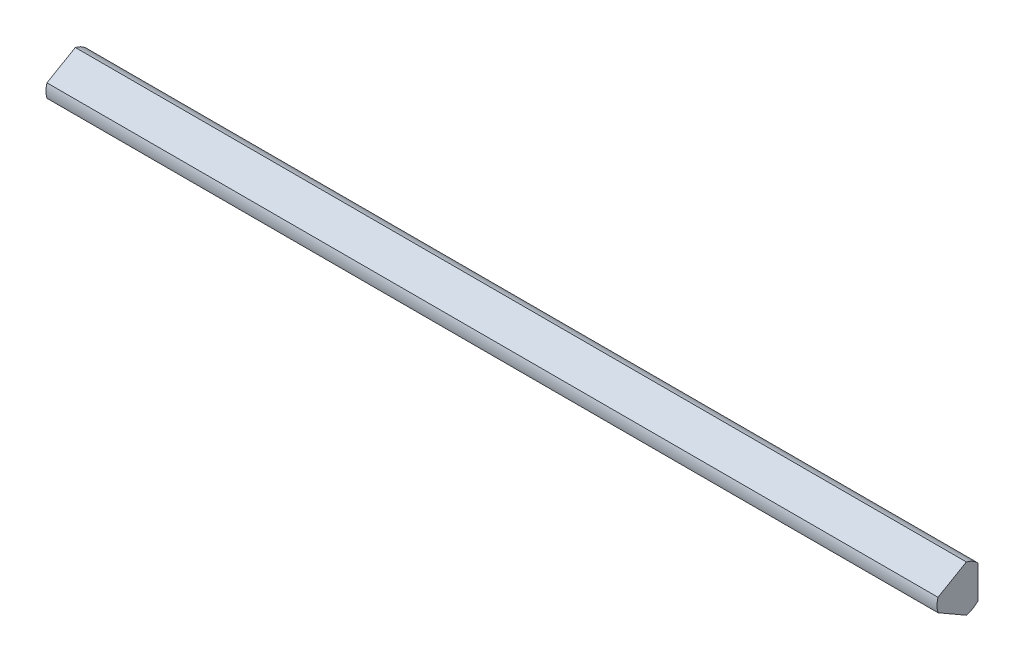
SolidWorks part; units mm, degrees
ref_plane "Plan de face" through (0, 0, 0) normal (0, 0, 1) x (1, 0, 0)
ref_plane "Plan de dessus" through (0, 0, 0) normal (0, 1, 0) x (1, 0, 0)
ref_plane "Plan de droite" through (0, 0, 0) normal (1, 0, 0) x (0, 0, -1)
ref_axis "Axe1" through (0, 0, 0) along (1, 0, 0)
sketch "Esquisse1" plane through (0, 0, 0) normal (1, 0, 0) x (0, 0, -1)
  line L6 (1.448, -1.3796) -> (1.448, 1.3796)
  line L7 (-1.9188, -0.5642) -> (0.4707, -1.9438)
  line L8 (0.4707, 1.9438) -> (-1.9188, 0.5642)
  arc A8 (1.448, 1.3796) -> (0.4707, 1.9438) centre (0, 0) ccw
  arc A9 (0.4707, -1.9438) -> (1.448, -1.3796) centre (0, 0) ccw
  arc A10 (-2, 0) -> (-1.9188, -0.5642) centre (0, 0) ccw
  arc A11 (-1.9188, 0.5642) -> (-2, 0) centre (0, 0) ccw
extrude "Boss.-Extru.1" add sketch "Esquisse1" along normal blind 75
ref_point "Point1"
ref_plane "SYM" through (37.5, 0, 0) normal (1, 0, 0) x (0, 0, -1)
